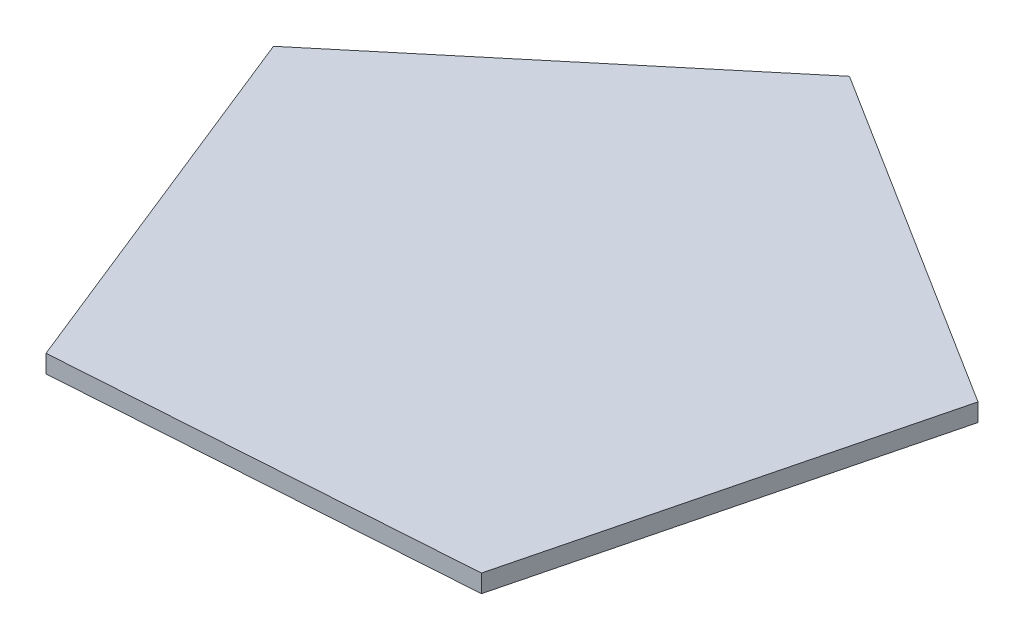
SolidWorks part; units mm, degrees
ref_plane "Front Plane" through (0, 0, 0) normal (0, 0, 1) x (1, 0, 0)
ref_plane "Top Plane" through (0, 0, 0) normal (0, 1, 0) x (1, 0, 0)
ref_plane "Right Plane" through (0, 0, 0) normal (1, 0, 0) x (0, 0, -1)
sketch "Sketch1" plane through (0, 0, 0) normal (0, 1, 0) x (1, 0, 0)
  line L1 (-59.9258, 15.1181) -> (-32.8962, -52.3211)
  line L2 (-32.8962, -52.3211) -> (39.5948, -47.4543)
  line L3 (39.5948, -47.4543) -> (57.3672, 22.9927)
  line L4 (57.3672, 22.9927) -> (-4.14, 61.6646)
  line L5 (-4.14, 61.6646) -> (-59.9258, 15.1181)
  circle A0 centre (0, 0) radius 50 construction
  dimension "D1" = 100
extrude "Boss-Extrude1" add sketch "Sketch1" along normal blind 3.18
equation "\"sheetThickness\"= 3.18mm"
equation "\"kerf\"= .22mm"
equation "\"halfkerf\"= \"kerf\"/ 2"
equation "\"tabThickness\" = \"kerf\" + \"sheetThickness\""
equation "\"D1@Boss-Extrude1\"=\"sheetThickness\""
equation "\"amountofcuts\" = 3"
equation "\"tabWidth\"= \"kerf\" + 10mm"
